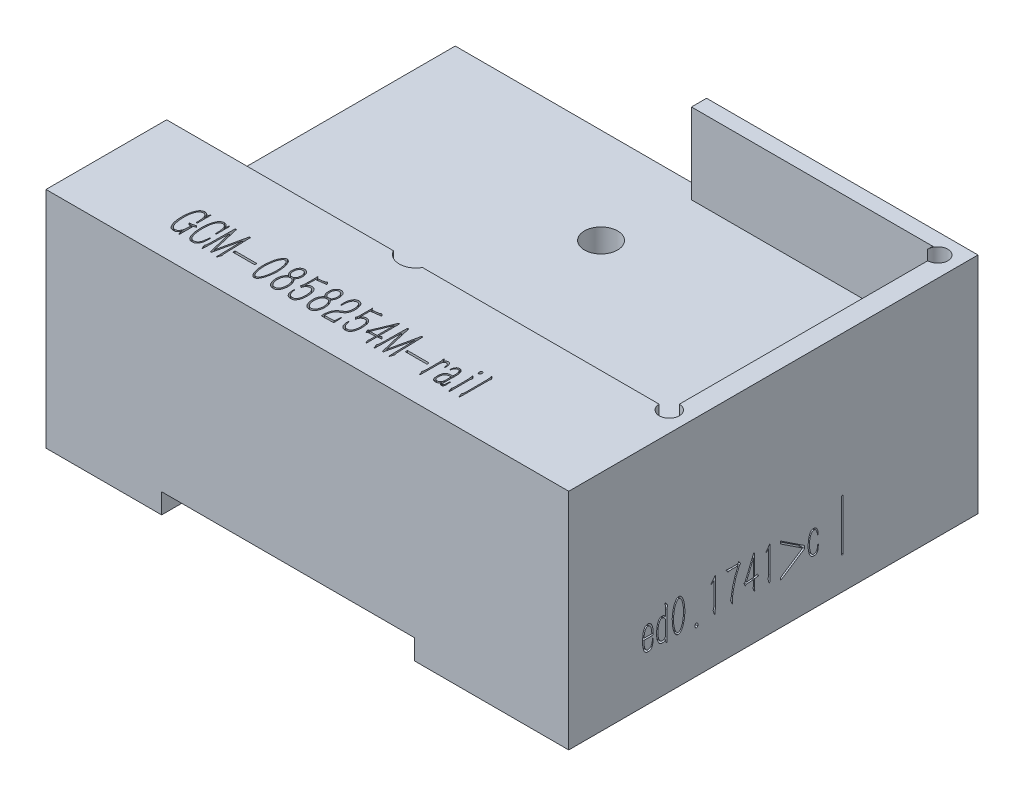
SolidWorks part; units mm, degrees
material "6061 合金"
ref_plane "前视基准面" through (0, 0, 0) normal (0, 0, 1) x (1, 0, 0)
ref_plane "上视基准面" through (0, 0, 0) normal (0, 1, 0) x (1, 0, 0)
ref_plane "右视基准面" through (0, 0, 0) normal (1, 0, 0) x (0, 0, -1)
sketch "草图1" plane through (0, 0, 0) normal (0, 1, 0) x (1, 0, 0)
  line L1 (-25, 13.355) -> (25, 13.355)
  line L2 (-25, 13.355) -> (-25, -13.355)
  line L3 (-25, -13.355) -> (25, -13.355)
  line L4 (25, 13.355) -> (25, -13.355)
  line L5 (-25, 13.355) -> (25, -13.355) construction
  line L6 (-25, -13.355) -> (25, 13.355) construction
  point P0 (0, 0)
  dimension "D1" = 50
  dimension "D2" = 26.71
extrude "凸台-拉伸1" add sketch "草图1" along normal blind 14.29
sketch "草图2" plane through (0, 14.29, 0) normal (0, 1, 0) x (1, 0, 0)
  line L1 (25, 13.355) -> (-25, 13.355) construction
  line L3 (25, 13.355) -> (-25, 13.355)
  line L12 (-25, -13.355) -> (25, -13.355) construction
  line L13 (-25, -13.355) -> (25, -13.355)
  line L19 (25, -13.355) -> (25, 13.355) construction
  line L20 (25, -13.355) -> (25, 13.355)
  line L21 (-25, -15.355) -> (27, -15.355)
  line L22 (27, -15.355) -> (27, 15.355)
  line L23 (27, 15.355) -> (-25, 15.355)
  line L24 (-25, -15.355) -> (-25, -13.355)
  line L25 (-25, 13.355) -> (-25, 15.355)
  dimension "D1" = 2
extrude "凸台-拉伸2" add sketch "草图2" along normal blind 8 and the other way through all
sketch "草图3" plane through (0, 14.29, 0) normal (0, 1, 0) x (1, 0, 0)
  line L0 (-1, 13.355) -> (-1, 5.855) construction
  line L1 (25, -13.355) -> (25, 13.355) construction
  line L3 (25, 13.355) -> (-25, 13.355) construction
  line L5 (-1, 5.855) -> (25, 5.855) construction
  circle A0 centre (-1, 5.855) radius 1.3881
  dimension "D1" = 7.5
  dimension "D2" = 26
hole_wizard "M4 螺纹孔1" positions "3D草图1" profile "草图4" tap size "M4" standard "GB"
sketch3d "3D草图1"
  point P0 (-1, 14.29, -5.855)
sketch "草图4" plane through (-1, 14.29, -5.855) normal (1, 0, 0) x (0, 0, 1)
  line L0 (0, 0) -> (0, 11.0914)
  line L1 (0, 11.0914) -> (1.65, 10.1)
  line L2 (1.65, 10.1) -> (1.65, 0)
  line L5 (1.65, 0) -> (0, 0)
  line L10 (0, 11.0914) -> (-1.65, 10.1) construction
  line L11 (0, -6.35) -> (0, 107.95) construction
  dimension "螺纹孔钻头直径" = 3.3
  dimension "螺纹孔钻头深度" = 10.1
  dimension "导头角度" = 118
cosmetic thread "孔螺蚊线1" parameters "D1"=2.4, "D2"=4
sketch "草图12" plane through (-25, 0, 0) normal (-1, 0, 0) x (0, 0, 1)
  line L1 (-13.355, 14.29) -> (-15.355, 14.29)
  line L2 (-13.355, 14.29) -> (-13.355, 22.29)
  line L3 (-13.355, 22.29) -> (-15.355, 22.29)
  line L4 (-15.355, 14.29) -> (-15.355, 22.29)
extrude "切除-拉伸5" cut sketch "草图12" against normal blind 25
sketch "草图13" plane through (0, 22.29, 0) normal (0, 1, 0) x (1, 0, 0)
  circle A0 centre (25, -13.355) radius 1
  circle A1 centre (25, 13.355) radius 1
extrude "切除-拉伸6" cut sketch "草图13" against normal up to surface (8 mm away) up to face at (-1, 14.29, -4.205)
sketch "草图15" plane through (0, 0, 15.355) normal (0, 0, 1) x (1, 0, 0)
  line L4 (27, 0) -> (27, 22.29)
  line L5 (27, 22.29) -> (-25, 22.29)
  line L6 (-25, 22.29) -> (-25, 0)
  line L7 (-25, 0) -> (27, 0)
  line L8 (27, 0) -> (27, 22.29)
  line L9 (27, 22.29) -> (-25, 22.29)
  line L10 (-25, 22.29) -> (-25, 0)
  line L11 (-25, 0) -> (27, 0)
  dimension "D1" = 0
extrude "凸台-拉伸3" add sketch "草图15" along normal blind 10
sketch "草图5" plane through (0, 0, 0) normal (0, -1, 0) x (1, 0, 0)
  line L1 (-13.4968, 25.0582) -> (11.5032, 25.0582)
  line L2 (-13.4968, 25.0582) -> (-13.4968, 0.0582)
  line L3 (-13.4968, 0.0582) -> (11.5032, 0.0582)
  line L4 (11.5032, 25.0582) -> (11.5032, 0.0582)
  line L5 (-13.4968, 25.0582) -> (11.5032, 0.0582) construction
  line L6 (-13.4968, 0.0582) -> (11.5032, 25.0582) construction
  line L8 (-13.4968, 0.0582) -> (-13.4968, 25.0518) construction
  line L9 (11.4968, 0.0582) -> (-13.4968, 0.0582) construction
  circle A0 centre (-0.9968, 12.5582) radius 1.1939
  dimension "D1" = 25
  dimension "D2" = 25
extrude "切除-拉伸1" cut sketch "草图5" against normal blind 2
sketch "草图6" plane through (0, 2, 0) normal (0, -1, 0) x (1, 0, 0)
  line L0 (-0.9968, 25.0582) -> (-0.9968, 0.0582) construction
  line L3 (-0.9968, 12.5582) -> (-13.4968, 12.5582) construction
  line L6 (-13.4968, 25.0582) -> (-13.4968, 0.0582) construction
  line L8 (11.5032, 25.0582) -> (-13.4968, 25.0582) construction
  dimension "D1" = 25
  dimension "D2" = 12.5
hole_wizard "M4 螺纹孔2" positions "3D草图2" profile "草图7" tap size "M4" standard "GB" end condition through all
sketch3d "3D草图2"
  point P0 (-0.9968, 2, 12.5582)
cosmetic thread "孔螺蚊线2" parameters "D2"=4
sketch "草图7" plane through (-0.9968, 2, 12.5582) normal (1, 0, 0) x (0, 0, -1)
  line L0 (0, 0) -> (0, 20.29)
  line L1 (0, 20.29) -> (1.65, 20.29)
  line L2 (1.65, 20.29) -> (1.65, 0)
  line L5 (1.65, 0) -> (0, 0)
  line L11 (0, -6.35) -> (0, 107.95) construction
  dimension "通孔螺纹孔钻头直径" = 3.3
  dimension "通孔螺纹孔钻头深度" = 20.29
sketch "草图16" plane through (0, 0, 25.0582) normal (0, 0, -1) x (-1, 0, 0)
  line L4 (-11.5032, 0) -> (13.4968, 0)
  line L5 (13.4968, 0) -> (13.4968, 2)
  line L6 (13.4968, 2) -> (-11.5032, 2)
  line L7 (-11.5032, 2) -> (-11.5032, 0)
  line L8 (-11.5032, 0) -> (13.4968, 0)
  line L9 (13.4968, 0) -> (13.4968, 2)
  line L10 (13.4968, 2) -> (-11.5032, 2)
  line L11 (-11.5032, 2) -> (-11.5032, 0)
  dimension "D1" = 0
extrude "切除-拉伸7" cut sketch "草图16" against normal through all
sketch "草图17" plane through (11.5032, 0, 0) normal (-1, 0, 0) x (0, 0, 1)
  line L4 (0.0582, 0) -> (25.355, 0)
  line L5 (25.355, 0) -> (25.355, 2)
  line L6 (25.355, 2) -> (0.0582, 2)
  line L7 (0.0582, 2) -> (0.0582, 0)
  line L8 (0.0582, 0) -> (25.355, 0)
  line L9 (25.355, 0) -> (25.355, 2)
  line L10 (25.355, 2) -> (0.0582, 2)
  line L11 (0.0582, 2) -> (0.0582, 0)
  dimension "D1" = 0
extrude "切除-拉伸8" [suppressed] cut sketch "草图17" against normal blind 0.17
sketch "草图18" plane through (0, 0, 0) normal (0, -1, 0) x (-1, 0, 0)
  circle A0 centre (13.4968, -0.0582) radius 1
extrude "切除-拉伸9" cut sketch "草图18" against normal up to surface (2 mm away) up to face at (-0.9968, 2, 10.9082)
fillet "圆角1" [suppressed] radius 1
sketch "草图19" plane through (0, 0, -13.355) normal (0, 0, 1) x (1, 0, 0)
  line L4 (24, 22.29) -> (0, 22.29)
  line L5 (0, 22.29) -> (0, 14.29)
  line L6 (0, 14.29) -> (24, 14.29)
  line L7 (24, 14.29) -> (24, 22.29)
  line L8 (24, 22.29) -> (0, 22.29)
  line L9 (0, 22.29) -> (0, 14.29)
  line L10 (0, 14.29) -> (24, 14.29)
  line L12 (24, 14.29) -> (24, 22.29)
  dimension "D1" = 0
extrude "切除-拉伸10" cut sketch "草图19" against normal blind 0.5
sketch "草图20" plane through (0, 22.29, 0) normal (0, 1, 0) x (1, 0, 0)
  text T0 "GCM-0858254M-rail"
extrude "切除-拉伸11" cut sketch "草图20" against normal blind 0.5
sketch "草图21" plane through (0, 14.29, 0) normal (0, 1, 0) x (1, 0, 0)
  line L0 (25, 0) -> (-1, 0) construction
  line L1 (25, 12.355) -> (25, -12.355) construction
  line L2 (-1, 0) -> (-1, 9.5574) construction
  dimension "D1" = 26
sketch "草图22" plane through (-25, 0, 0) normal (-1, 0, 0) x (0, 0, 1)
  text T0 "| cen"
extrude "切除-拉伸12" cut sketch "草图22" against normal blind 0.5
sketch "草图24" plane through (27, 0, 0) normal (1, 0, 0) x (0, 0, -1)
  text T0 "ed0.1741>c |"
extrude "切除-拉伸14" cut sketch "草图24" against normal blind 0.5
sketch "草图25" plane through (11.5032, 0, 0) normal (-1, 0, 0) x (0, 0, 1)
  line L4 (0.0582, 0) -> (25.355, 0)
  line L5 (25.355, 0) -> (25.355, 2)
  line L6 (25.355, 2) -> (0.0582, 2)
  line L7 (0.0582, 2) -> (0.0582, 0)
  line L8 (0.0582, 0) -> (25.355, 0)
  line L9 (25.355, 0) -> (25.355, 2)
  line L10 (25.355, 2) -> (0.0582, 2)
  line L11 (0.0582, 2) -> (0.0582, 0)
  dimension "D1" = 0
extrude "切除-拉伸15" cut sketch "草图25" against normal blind 0.1741
sketch "草图23" plane through (0, 0, 0) normal (0, -1, 0) x (-1, 0, 0)
  circle A0 centre (-11.6773, -0.0582) radius 1
  point P3 (0, 0)
extrude "切除-拉伸13" cut sketch "草图23" against normal up to surface (2 mm away) up to face at (-3.4686, 2, 10.1355)
